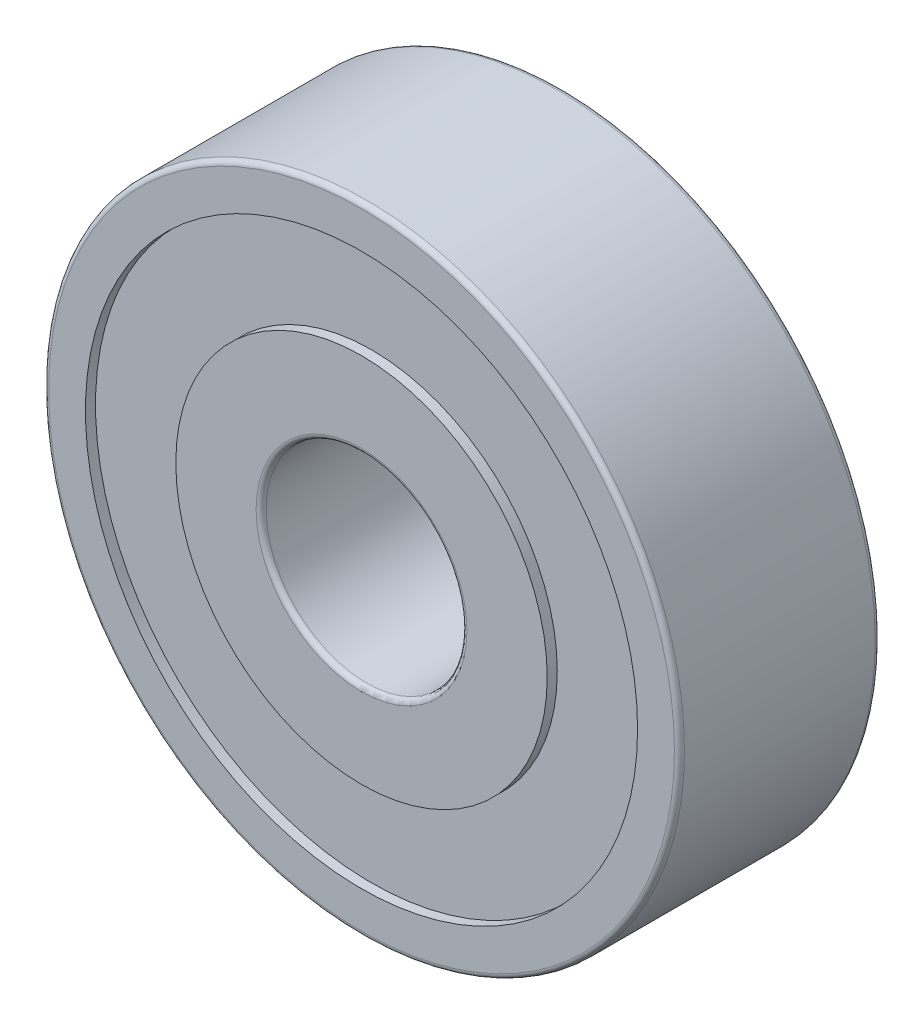
SolidWorks part; units mm, degrees
ref_plane "Front Plane" through (0, 0, 0) normal (0, 0, 1) x (1, 0, 0)
ref_plane "Top Plane" through (0, 0, 0) normal (0, 1, 0) x (1, 0, 0)
ref_plane "Right Plane" through (0, 0, 0) normal (1, 0, 0) x (0, 0, -1)
sketch "Sketch1" plane through (0, 0, 0) normal (0, 0, 1) x (1, 0, 0)
  circle A0 centre (0, 0) radius 3
  circle A1 centre (0, 0) radius 9.5
  dimension "D1" = 6
  dimension "D2" = 19
extrude "Boss-Extrude1" add sketch "Sketch1" along normal blind 6
sketch "Sketch2" plane through (0, 0, 6) normal (0, 0, 1) x (1, 0, 0)
  circle A3 centre (0, 0) radius 8.25
  circle A6 centre (0, 0) radius 5.55
  dimension "D1" = 11.1
  dimension "D2" = 16.5
extrude "Cut-Extrude1" cut sketch "Sketch2" against normal blind 0.3
extrude "Cut-Extrude2" cut sketch "Sketch2<2>" along normal blind 0.5 from surface starting at face at (9.5, 0, 0)
sketch "Sketch2<2>" plane through (0, 0, 6) normal (0, 0, 1) x (1, 0, 0) same geometry as "Sketch2"
fillet "Fillet1" radius 0.15 4 edges at (3, 0, 6) (9.5, 0, 6) (3, 0, 0) (9.5, 0, 0)
